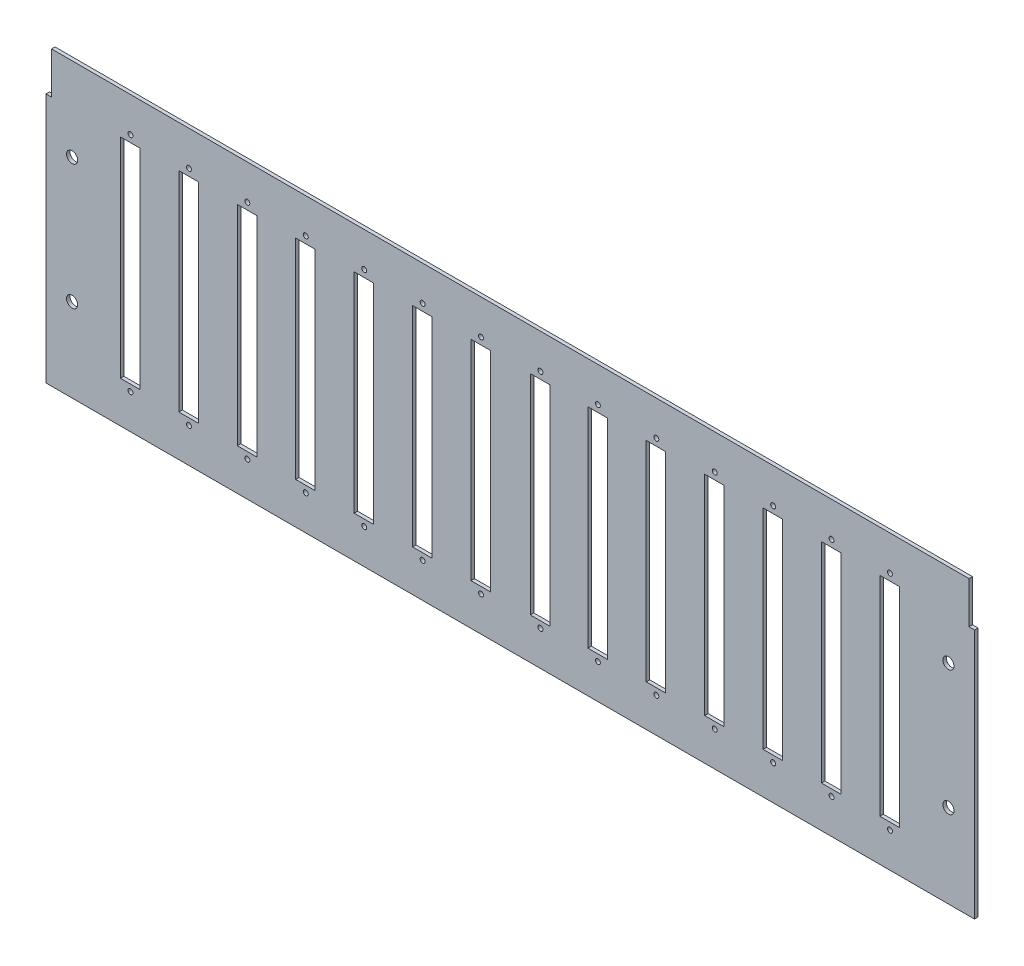
SolidWorks part; units mm, degrees
ref_plane "Front Plane" through (0, 0, 0) normal (0, 0, 1) x (1, 0, 0)
ref_plane "Top Plane" through (0, 0, 0) normal (0, 1, 0) x (1, 0, 0)
ref_plane "Right Plane" through (0, 0, 0) normal (1, 0, 0) x (0, 0, -1)
sketch "Sketch1" plane through (0, 0, 0) normal (0, 0, 1) x (1, 0, 0)
  line L0 (0, 0) -> (0, 114.3)
  line L5 (0, 0) -> (423.8752, 0)
  line L7 (2.54, 133.35) -> (421.3352, 133.35)
  line L9 (33.9788, 114.3) -> (42.8688, 114.3)
  line L10 (33.9788, 114.3) -> (33.9788, 18.8595)
  line L11 (33.9788, 18.8595) -> (42.8688, 18.8595)
  line L12 (42.8688, 114.3) -> (42.8688, 18.8595)
  line L13 (423.8752, 0) -> (423.8752, 114.3)
  line L30 (60.6488, 114.3) -> (69.5388, 114.3)
  line L31 (60.6488, 114.3) -> (60.6488, 18.8595)
  line L32 (60.6488, 18.8595) -> (69.5388, 18.8595)
  line L33 (69.5388, 114.3) -> (69.5388, 18.8595)
  line L34 (87.3188, 114.3) -> (96.2088, 114.3)
  line L35 (87.3188, 114.3) -> (87.3188, 18.8595)
  line L36 (87.3188, 18.8595) -> (96.2088, 18.8595)
  line L37 (96.2088, 114.3) -> (96.2088, 18.8595)
  line L38 (113.9888, 114.3) -> (122.8788, 114.3)
  line L39 (113.9888, 114.3) -> (113.9888, 18.8595)
  line L40 (113.9888, 18.8595) -> (122.8788, 18.8595)
  line L41 (122.8788, 114.3) -> (122.8788, 18.8595)
  line L42 (140.6588, 114.3) -> (149.5488, 114.3)
  line L43 (140.6588, 114.3) -> (140.6589, 18.8595)
  line L44 (140.6589, 18.8595) -> (149.5488, 18.8595)
  line L45 (149.5488, 114.3) -> (149.5488, 18.8595)
  line L46 (247.3389, 114.3) -> (256.2289, 114.3)
  line L47 (247.3389, 114.3) -> (247.3389, 18.8595)
  line L48 (247.3389, 18.8595) -> (256.2289, 18.8595)
  line L49 (256.2289, 114.3) -> (256.2289, 18.8595)
  line L50 (167.3288, 114.3) -> (176.2188, 114.3)
  line L51 (167.3288, 114.3) -> (167.3288, 18.8595)
  line L52 (167.3288, 18.8595) -> (176.2188, 18.8595)
  line L53 (176.2188, 114.3) -> (176.2188, 18.8595)
  line L54 (193.9988, 114.3) -> (202.8888, 114.3)
  line L55 (193.9988, 114.3) -> (193.9989, 18.8595)
  line L56 (193.9989, 18.8595) -> (202.8888, 18.8595)
  line L57 (202.8888, 114.3) -> (202.8888, 18.8595)
  line L58 (221.1004, 114.3) -> (229.9904, 114.3)
  line L59 (221.1004, 114.3) -> (221.1004, 18.8595)
  line L60 (221.1004, 18.8595) -> (229.9904, 18.8595)
  line L61 (229.9904, 114.3) -> (229.9904, 18.8595)
  line L62 (274.0088, 114.3) -> (282.8988, 114.3)
  line L63 (274.0088, 114.3) -> (274.0088, 18.8595)
  line L64 (274.0088, 18.8595) -> (282.8988, 18.8595)
  line L65 (282.8988, 114.3) -> (282.8988, 18.8595)
  line L66 (300.6788, 114.3) -> (309.5688, 114.3)
  line L67 (300.6788, 114.3) -> (300.6788, 18.8595)
  line L92 (300.6788, 18.8595) -> (309.5688, 18.8595)
  line L93 (309.5688, 114.3) -> (309.5688, 18.8595)
  line L94 (327.3488, 114.3) -> (336.2388, 114.3)
  line L95 (327.3488, 114.3) -> (327.3488, 18.8595)
  line L96 (327.3488, 18.8595) -> (336.2388, 18.8595)
  line L97 (336.2388, 114.3) -> (336.2388, 18.8595)
  line L98 (354.0188, 114.3) -> (362.9088, 114.3)
  line L99 (354.0188, 114.3) -> (354.0188, 18.8595)
  line L100 (354.0188, 18.8595) -> (362.9088, 18.8595)
  line L101 (362.9088, 114.3) -> (362.9088, 18.8595)
  line L102 (380.6888, 114.3) -> (389.5788, 114.3)
  line L103 (380.6888, 114.3) -> (380.6888, 19.05)
  line L104 (380.6888, 19.05) -> (389.5788, 19.05)
  line L105 (389.5788, 114.3) -> (389.5788, 19.05)
  line L106 (0, 114.3) -> (2.54, 114.3)
  line L107 (2.54, 114.3) -> (2.54, 133.35)
  line L110 (423.8752, 114.3) -> (421.3352, 114.3)
  line L111 (421.3352, 114.3) -> (421.3352, 133.35)
  circle A0 centre (11.9126, 38.1) radius 2.54
  circle A1 centre (11.9126, 95.25) radius 2.54
  circle A2 centre (411.9626, 95.25) radius 2.54
  circle A3 centre (411.9626, 38.1) radius 2.54
  circle A4 centre (38.5826, 117.475) radius 1.1303
  circle A5 centre (38.5826, 15.875) radius 1.1303
  circle A6 centre (65.2526, 117.475) radius 1.1303
  circle A7 centre (65.2526, 15.875) radius 1.1303
  circle A8 centre (91.9226, 117.475) radius 1.1303
  circle A9 centre (91.9226, 15.875) radius 1.1303
  circle A10 centre (118.5926, 117.475) radius 1.1303
  circle A11 centre (118.5926, 15.875) radius 1.1303
  circle A12 centre (145.2626, 117.475) radius 1.1303
  circle A13 centre (145.2626, 15.875) radius 1.1303
  circle A14 centre (171.9326, 117.475) radius 1.1303
  circle A15 centre (171.9326, 15.875) radius 1.1303
  circle A16 centre (198.6026, 117.475) radius 1.1303
  circle A17 centre (198.6026, 15.875) radius 1.1303
  circle A18 centre (225.7042, 117.475) radius 1.1303
  circle A19 centre (225.7042, 15.875) radius 1.1303
  circle A32 centre (251.9426, 117.475) radius 1.1303
  circle A33 centre (251.9426, 15.875) radius 1.1303
  circle A34 centre (278.6126, 117.475) radius 1.1303
  circle A35 centre (278.6126, 15.875) radius 1.1303
  circle A36 centre (305.2826, 117.475) radius 1.1303
  circle A37 centre (305.2826, 15.875) radius 1.1303
  circle A38 centre (331.9526, 117.475) radius 1.1303
  circle A39 centre (331.9526, 15.875) radius 1.1303
  circle A40 centre (358.6226, 117.475) radius 1.1303
  circle A41 centre (358.6226, 15.875) radius 1.1303
  circle A42 centre (385.2926, 117.475) radius 1.1303
  circle A43 centre (385.2926, 15.875) radius 1.1303
  point P3 (-37.6216, 86.8914)
  point P21 (64.6976, 38.9661)
  point P22 (0, 0)
  point P23 (251.7839, 18.8595)
  point P24 (-188.1638, 127.0051)
  dimension "D3" = 400.05
  dimension "D7" = 38.5826
  dimension "D8" = 8.89
  dimension "D13" = 5.08
  dimension "D14" = 26.67
  dimension "D30" = 2.2606
  dimension "D9" = 5.08
  dimension "D2" = 2.54
  dimension "D4" = 11.9126
  dimension "D5" = 33.9788
  dimension "D6" = 26.67
  dimension "D10" = 57.15
  dimension "D11" = 38.1
  dimension "D12" = 133.35
  dimension "D15" = 95.25
  dimension "D16" = 8.89
  dimension "D17" = 19.05
  dimension "D18" = 8.89
  dimension "D19" = 8.89
  dimension "D20" = 8.89
  dimension "D21" = 8.89
  dimension "D22" = 8.89
  dimension "D23" = 8.89
  dimension "D24" = 8.89
  dimension "D25" = 8.89
  dimension "D26" = 8.89
  dimension "D27" = 8.89
  dimension "D28" = 8.89
  dimension "D29" = 8.89
  dimension "D31" = 423.8752
extrude "Boss-Extrude1" add sketch "Sketch1" along normal blind 1.5875 contours L5 L7 A43 L104 L103 L102 L105 A42 A41 A40 A39 A38 A37 A36 A35 A34 A33 A32 A19 A18 A17 A16 A15 A14 A13 A12 A11 region at (211.9784, 66.574, 0)
